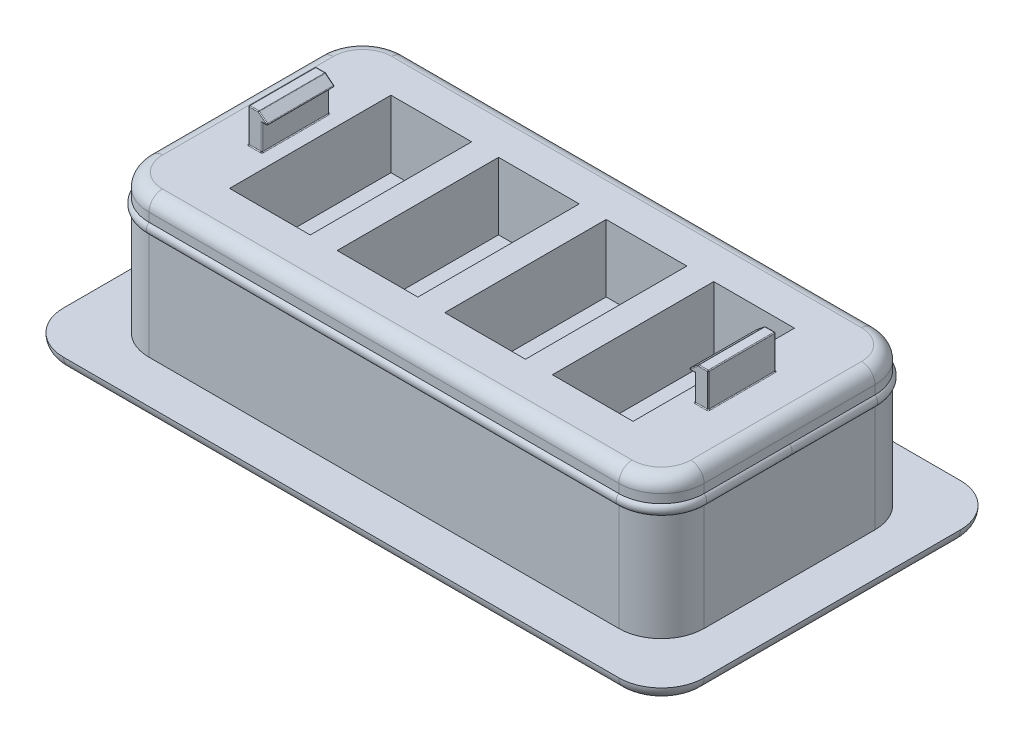
SolidWorks part; units mm, degrees
ref_plane "Front Plane" through (0, 0, 0) normal (0, 0, 1) x (1, 0, 0)
ref_plane "Top Plane" through (0, 0, 0) normal (0, 1, 0) x (1, 0, 0)
ref_plane "Right Plane" through (0, 0, 0) normal (1, 0, 0) x (0, 0, -1)
sketch "Sketch1" plane through (0, 0, 0) normal (0, 1, 0) x (1, 0, 0)
  line L1 (41.275, 19.05) -> (-41.275, 19.05)
  line L2 (41.275, 19.05) -> (41.275, -19.05)
  line L3 (41.275, -19.05) -> (-41.275, -19.05)
  line L4 (-41.275, 19.05) -> (-41.275, -19.05)
  line L5 (41.275, 19.05) -> (-41.275, -19.05) construction
  line L6 (41.275, -19.05) -> (-41.275, 19.05) construction
  point P0 (0, 0)
  dimension "D1" = 38.1
  dimension "D2" = 82.55
extrude "Boss-Extrude1" add sketch "Sketch1" along normal blind 12.7
sketch "Sketch2" plane through (0, 0, 0) normal (0, -1, 0) x (1, 0, 0)
  line L12 (-47.625, 25.4) -> (-47.625, -25.4)
  line L13 (-47.625, -25.4) -> (47.625, -25.4)
  line L14 (47.625, -25.4) -> (47.625, 25.4)
  line L15 (47.625, 25.4) -> (-47.625, 25.4)
  line L16 (-47.625, 25.4) -> (-47.625, -25.4)
  line L17 (-47.625, -25.4) -> (47.625, -25.4)
  line L18 (47.625, -25.4) -> (47.625, 25.4)
  line L19 (47.625, 25.4) -> (-47.625, 25.4)
  dimension "D1" = 6.35
extrude "Boss-Extrude2" add sketch "Sketch2" against normal blind 2
shell "Shell1" thickness 2 removed face at (0, 0, 0)
sketch "Sketch3" plane through (0, 10.7, 0) normal (0, -1, 0) x (1, 0, 0)
  line L0 (0, 0) -> (0, -17.05) construction
  line L1 (-27.175, 4.5339) -> (-20.825, 4.5339)
  line L2 (-27.175, 4.5339) -> (-27.175, -4.5339)
  line L3 (-27.175, -4.5339) -> (-20.825, -4.5339)
  line L4 (-20.825, 4.5339) -> (-20.825, -4.5339)
  line L5 (-27.175, 4.5339) -> (-20.825, -4.5339) construction
  line L6 (-27.175, -4.5339) -> (-20.825, 4.5339) construction
  line L7 (-11.175, 4.5339) -> (-4.825, 4.5339)
  line L8 (-11.175, 4.5339) -> (-11.175, -4.5339)
  line L9 (-11.175, -4.5339) -> (-4.825, -4.5339)
  line L10 (-4.825, 4.5339) -> (-4.825, -4.5339)
  line L11 (-11.175, 4.5339) -> (-4.825, -4.5339) construction
  line L12 (-11.175, -4.5339) -> (-4.825, 4.5339) construction
  line L13 (4.825, 4.5339) -> (11.175, 4.5339)
  line L14 (4.825, 4.5339) -> (4.825, -4.5339)
  line L15 (4.825, -4.5339) -> (11.175, -4.5339)
  line L16 (11.175, 4.5339) -> (11.175, -4.5339)
  line L17 (4.825, 4.5339) -> (11.175, -4.5339) construction
  line L18 (4.825, -4.5339) -> (11.175, 4.5339) construction
  line L19 (20.825, 4.5339) -> (27.175, 4.5339)
  line L20 (20.825, 4.5339) -> (20.825, -4.5339)
  line L21 (20.825, -4.5339) -> (27.175, -4.5339)
  line L22 (27.175, 4.5339) -> (27.175, -4.5339)
  line L23 (20.825, 4.5339) -> (27.175, -4.5339) construction
  line L24 (20.825, -4.5339) -> (27.175, 4.5339) construction
  line L25 (-39.275, -17.05) -> (39.275, -17.05) construction
  line L26 (-24, 0) -> (24, 0) construction
  point P0 (-24, 0)
  point P5 (-8, 0)
  point P10 (8, 0)
  point P15 (24, 0)
  dimension "D1" = 6.35
  dimension "D2" = 9.0678
  dimension "D3" = 16
  dimension "D4" = 16
extrude "Cut-Extrude1" cut sketch "Sketch3" against normal through all both and the other way through all
fillet "Fillet1" radius 6.35 12 edges at (-47.625, 1, 25.4) (-47.625, 1, -25.4) (47.625, 1, -25.4) (47.625, 1, 25.4) (-41.275, 7.35, -19.05) (41.275, 7.35, -19.05) (-41.275, 7.35, 19.05) (41.275, 7.35, 19.05) (-39.275, 5.35, 17.05) (39.275, 5.35, 17.05) (-39.275, 5.35, -17.05) (39.275, 5.35, -17.05)
fillet "Fillet2" radius 2 16 edges at (45.7651, 0, 23.5401) (47.625, 0, 0) (45.7651, 0, -23.5401) (0, 0, -25.4) (-45.7651, 0, -23.5401) (-47.625, 0, 0) (-45.7651, 0, 23.5401) (0, 0, 25.4) (39.275, 0, 0) (0, 0, 17.05) (-39.275, 0, 0) (0, 0, -17.05) (37.4151, 0, -15.1901) (37.4151, 0, 15.1901) (-37.4151, 0, 15.1901) (-37.4151, 0, -15.1901)
chamfer "Chamfer1" distance 2 angle 45 16 edges at (24, 10.7, 4.5339) (20.825, 10.7, 0) (24, 10.7, -4.5339) (27.175, 10.7, 0) (8, 10.7, 4.5339) (4.825, 10.7, 0) (8, 10.7, -4.5339) (11.175, 10.7, 0) (-8, 10.7, 4.5339) (-11.175, 10.7, 0) (-8, 10.7, -4.5339) (-4.825, 10.7, 0) (-24, 10.7, 4.5339) (-27.175, 10.7, 0) (-24, 10.7, -4.5339) (-20.825, 10.7, 0)
sketch "Sketch4" plane through (0, 12.7, 0) normal (0, 1, 0) x (1, 0, 0)
  line L0 (24, 4.5339) -> (24, -4.5339) construction
  line L7 (20.825, 4.5339) -> (27.175, 4.5339) construction
  line L8 (27.175, -4.5339) -> (20.825, -4.5339) construction
  line L9 (8, -4.5339) -> (8, 4.5339) construction
  line L10 (18, -12) -> (30, -12)
  line L11 (18, -12) -> (18, 12)
  line L12 (18, 12) -> (30, 12)
  line L13 (30, -12) -> (30, 12)
  line L14 (18, -12) -> (30, 12) construction
  line L15 (18, 12) -> (30, -12) construction
  line L16 (11.175, -4.5339) -> (4.825, -4.5339) construction
  line L17 (4.825, 4.5339) -> (11.175, 4.5339) construction
  line L18 (-8, -4.5339) -> (-8, 4.5339) construction
  line L19 (-4.825, -4.5339) -> (-11.175, -4.5339) construction
  line L20 (-11.175, 4.5339) -> (-4.825, 4.5339) construction
  line L21 (-24, -4.5339) -> (-24, 4.5339) construction
  line L22 (-20.825, -4.5339) -> (-27.175, -4.5339) construction
  line L23 (-27.175, 4.5339) -> (-20.825, 4.5339) construction
  line L25 (2, -12) -> (14, -12)
  line L26 (2, -12) -> (2, 12)
  line L27 (2, 12) -> (14, 12)
  line L28 (14, -12) -> (14, 12)
  line L29 (2, -12) -> (14, 12) construction
  line L30 (2, 12) -> (14, -12) construction
  line L31 (-14, -12) -> (-2, -12)
  line L32 (-14, -12) -> (-14, 12)
  line L33 (-14, 12) -> (-2, 12)
  line L34 (-2, -12) -> (-2, 12)
  line L35 (-14, -12) -> (-2, 12) construction
  line L36 (-14, 12) -> (-2, -12) construction
  line L37 (-30, -12) -> (-18, -12)
  line L38 (-30, -12) -> (-30, 12)
  line L39 (-30, 12) -> (-18, 12)
  line L40 (-18, -12) -> (-18, 12)
  line L41 (-30, -12) -> (-18, 12) construction
  line L42 (-30, 12) -> (-18, -12) construction
  line L44 (34.925, 19.05) -> (-34.925, 19.05)
  line L45 (-41.275, 12.7) -> (-41.275, -12.7)
  line L46 (-34.925, -19.05) -> (34.925, -19.05)
  line L47 (41.275, -12.7) -> (41.275, 12.7)
  line L48 (34.925, 19.05) -> (-34.925, 19.05)
  line L49 (-41.275, 12.7) -> (-41.275, -12.7)
  line L50 (-34.925, -19.05) -> (34.925, -19.05)
  line L51 (41.275, -12.7) -> (41.275, 12.7)
  arc A4 (-34.925, 19.05) -> (-41.275, 12.7) centre (-34.925, 12.7) ccw
  arc A5 (-41.275, -12.7) -> (-34.925, -19.05) centre (-34.925, -12.7) ccw
  arc A6 (34.925, -19.05) -> (41.275, -12.7) centre (34.925, -12.7) ccw
  arc A7 (41.275, 12.7) -> (34.925, 19.05) centre (34.925, 12.7) ccw
  arc A8 (-34.925, 19.05) -> (-41.275, 12.7) centre (-34.925, 12.7) ccw
  arc A9 (-41.275, -12.7) -> (-34.925, -19.05) centre (-34.925, -12.7) ccw
  arc A10 (34.925, -19.05) -> (41.275, -12.7) centre (34.925, -12.7) ccw
  arc A11 (41.275, 12.7) -> (34.925, 19.05) centre (34.925, 12.7) ccw
  point P0 (0, 0)
  point P12 (24, 0)
  point P35 (8, 0)
  point P40 (-8, 0)
  point P45 (-24, 0)
  dimension "D1" = 0
  dimension "D3" = 24
  dimension "D4" = 12
extrude "Boss-Extrude3" add sketch "Sketch4" along normal blind 9.98
sketch "Sketch5" plane through (0, 0, 0) normal (0, 0, 1) x (1, 0, 0)
  line L5 (41.275, 2) -> (41.275, 22.68) construction
  line L6 (47.625, 2) -> (41.275, 2) construction
  line L7 (41.275, 19.375) -> (41.275, 17.875)
  arc A0 (41.275, 19.375) -> (41.275, 17.875) centre (40.7273, 18.625) cw
  point P8 (41.656, 18.625)
  dimension "D1" = 15.875
  dimension "D2" = 0.381
  dimension "D3" = 1.5
sketch "Sketch6" plane through (0, 22.68, 0) normal (0, 1, 0) x (1, 0, 0)
  line L4 (34.925, 19.05) -> (-34.925, 19.05)
  line L5 (-41.275, 12.7) -> (-41.275, -12.7)
  line L6 (-34.925, -19.05) -> (34.925, -19.05)
  line L7 (41.275, -12.7) -> (41.275, 12.7)
  line L8 (34.925, 19.05) -> (-34.925, 19.05)
  line L9 (-41.275, 12.7) -> (-41.275, -12.7)
  line L10 (-34.925, -19.05) -> (34.925, -19.05)
  line L11 (41.275, -12.7) -> (41.275, 12.7)
  arc A4 (41.275, 12.7) -> (34.925, 19.05) centre (34.925, 12.7) ccw
  arc A5 (-34.925, 19.05) -> (-41.275, 12.7) centre (-34.925, 12.7) ccw
  arc A6 (-41.275, -12.7) -> (-34.925, -19.05) centre (-34.925, -12.7) ccw
  arc A7 (34.925, -19.05) -> (41.275, -12.7) centre (34.925, -12.7) ccw
  arc A8 (41.275, 12.7) -> (34.925, 19.05) centre (34.925, 12.7) ccw
  arc A9 (-34.925, 19.05) -> (-41.275, 12.7) centre (-34.925, 12.7) ccw
  arc A10 (-41.275, -12.7) -> (-34.925, -19.05) centre (-34.925, -12.7) ccw
  arc A11 (34.925, -19.05) -> (41.275, -12.7) centre (34.925, -12.7) ccw
  dimension "D1" = 0
sweep "Sweep1" add profiles "Sketch5" path "Sketch6"
sketch "Sketch8" plane through (0, 0, 0) normal (0, 0, 1) x (1, 0, 0)
  line L0 (34.1798, 22.68) -> (34.1798, 27.76)
  line L2 (34.1798, 27.76) -> (32.6798, 27.76)
  line L3 (32.6798, 27.76) -> (31.1798, 26.535)
  line L4 (31.1798, 26.535) -> (32.1798, 26.535)
  line L5 (32.1798, 26.535) -> (32.1798, 22.68)
  line L6 (32.1798, 22.68) -> (34.1798, 22.68)
  line L7 (32, 24.77) -> (32, 26.37) construction
  line L8 (32, 26.37) -> (31.337, 26.37) construction
  line L9 (41.275, 2) -> (41.275, 17.875) construction
  line L10 (34.925, 22.68) -> (-34.925, 22.68) construction
  dimension "D1" = 2
  dimension "D2" = 5.08
  dimension "D3" = 0.165
  dimension "D4" = 0.1798
  dimension "D5" = 9.0952
  dimension "D6" = 3.855
  dimension "D7" = 1
  dimension "D8" = 1.5
extrude "Boss-Extrude4" add sketch "Sketch8" along normal mid plane 10
fillet "Fillet3" radius 0.125 17 edges at (32.1798, 22.68, 0) (32.1798, 24.6075, 5) (31.6798, 26.535, 5) (31.9298, 27.1475, 5) (33.1798, 22.68, 5) (34.1798, 22.68, 0) (34.1798, 25.22, 5) (34.1798, 25.22, -5) (31.9298, 27.1475, -5) (31.6798, 26.535, -5) (32.1798, 24.6075, -5) (33.1798, 22.68, -5) (34.1798, 27.76, 0) (33.4298, 27.76, 5) (32.6798, 27.76, 0) (33.4298, 27.76, -5) (31.1798, 26.535, 0)
mirror "Mirror1" about plane through (0, 0, 0) normal (1, 0, 0) of "Boss-Extrude4", "Fillet3"
fillet "Fillet4" radius 2 8 edges at (-39.4151, 22.68, 17.1901) (-41.275, 22.68, 0) (-39.4151, 22.68, -17.1901) (0, 22.68, -19.05) (39.4151, 22.68, -17.1901) (41.275, 22.68, 0) (39.4151, 22.68, 17.1901) (0, 22.68, 19.05)
